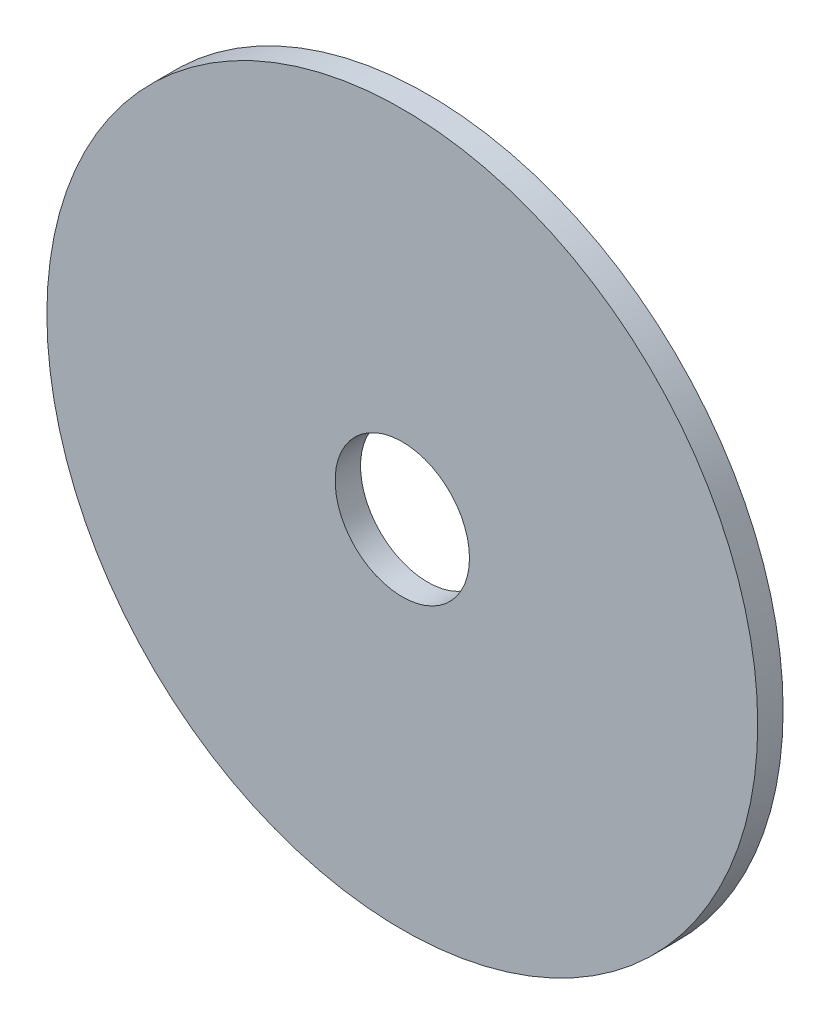
SolidWorks part; units mm, degrees
ref_plane "Front Plane" through (0, 0, 0) normal (0, 0, 1) x (1, 0, 0)
ref_plane "Top Plane" through (0, 0, 0) normal (0, 1, 0) x (1, 0, 0)
ref_plane "Right Plane" through (0, 0, 0) normal (1, 0, 0) x (0, 0, -1)
sketch "Sketch1" plane through (0, 0, 0) normal (0, 0, 1) x (1, 0, 0)
  line L0 (-22.225, 0) -> (22.225, 0) construction
  line L1 (-4.2, 0) -> (4.2, 0) construction
  circle A0 centre (0, 0) radius 4.2 construction
  circle A1 centre (0, 0) radius 22.225 construction
  point P8 (0, 0)
  point P9 (0, 22.225)
  point P11 (4.2, 0)
  dimension "ID" = 8.4
  dimension "OD" = 44.45
sketch "Sketch2" plane through (0, 0, 0) normal (1, 0, 0) x (0, 0, -1)
  line L0 (-1.025, 22.225) -> (1.025, 22.225) construction
  point P2 (0, 22.225)
  dimension "Thickness" = 2.05
sketch "Sketch3" plane through (0, 0, 0) normal (0, 0, 1) x (1, 0, 0)
  circle A0 centre (0, 0) radius 4.2
  circle A1 centre (0, 0) radius 22.225
extrude "Boss-Extrude1" add sketch "Sketch3" along normal blind 1.5875
ref_axis "Center Axis 1" through (0, 0, 1.5875) along (0, 0, -1)
